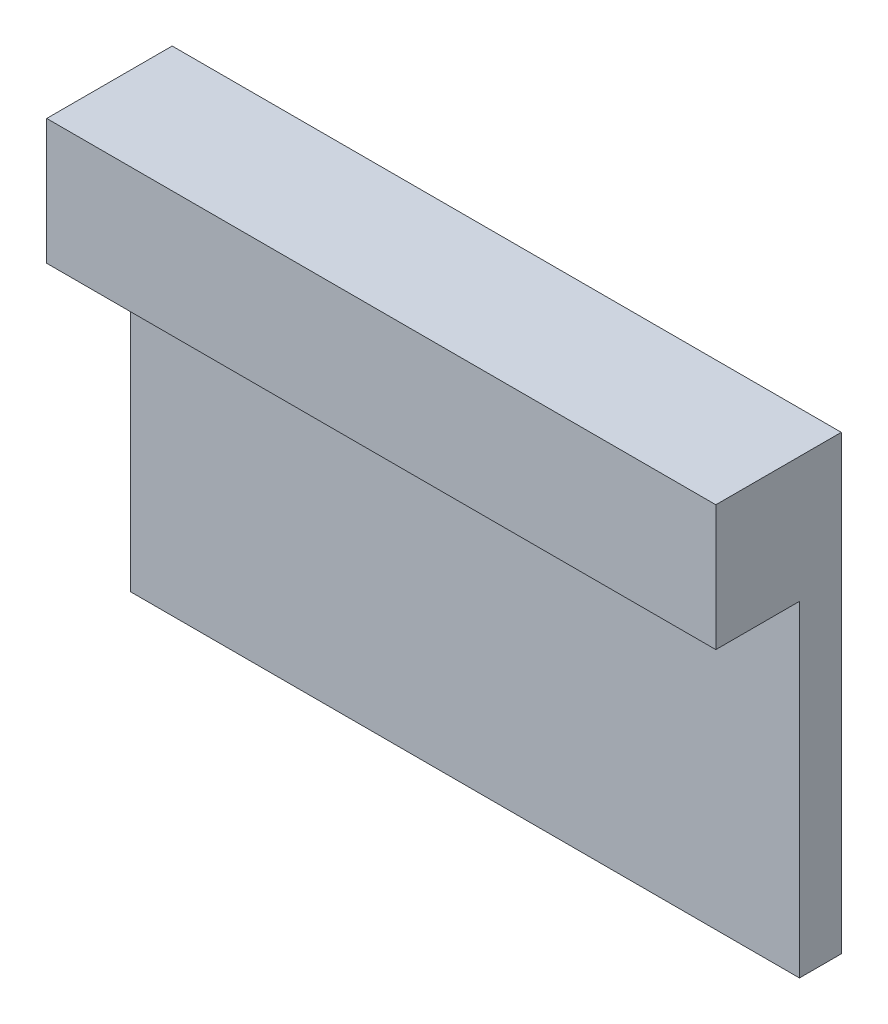
SolidWorks part; units mm, degrees
ref_plane "Plan de face" through (0, 0, 0) normal (0, 0, 1) x (1, 0, 0)
ref_plane "Plan de dessus" through (0, 0, 0) normal (0, 1, 0) x (1, 0, 0)
ref_plane "Plan de droite" through (0, 0, 0) normal (1, 0, 0) x (0, 0, -1)
sketch "Sketch2" plane through (0, 0, 0) normal (0, 0, 1) x (1, 0, 0)
  line L1 (32.82, 60.8812) -> (192.82, 60.8812)
  line L2 (32.82, 60.8812) -> (32.82, -17.1188)
  line L3 (32.82, -17.1188) -> (192.82, -17.1188)
  line L4 (192.82, 60.8812) -> (192.82, -17.1188)
  line L5 (32.82, 90.8812) -> (192.82, 90.8812)
  line L6 (32.82, 90.8812) -> (32.82, 60.8812)
  line L7 (32.82, 60.8812) -> (192.82, 60.8812)
  line L8 (192.82, 90.8812) -> (192.82, 60.8812)
  dimension "D1" = 30
  dimension "D2" = 78
  dimension "D3" = 160
  dimension "D4" = 160
extrude "Boss-Extrude1" add sketch "Sketch2" along normal blind 10 contours L4 L1 L2 L3 region at (112.82, 21.8812, 0)
extrude "Boss-Extrude2" add sketch "Sketch2<3>" along normal blind 30 contours L8 L5 L6 L1 region at (112.82, 75.8812, 0)
sketch "Sketch2<3>" plane through (0, 0, 0) normal (0, 0, 1) x (1, 0, 0) same geometry as "Sketch2"
